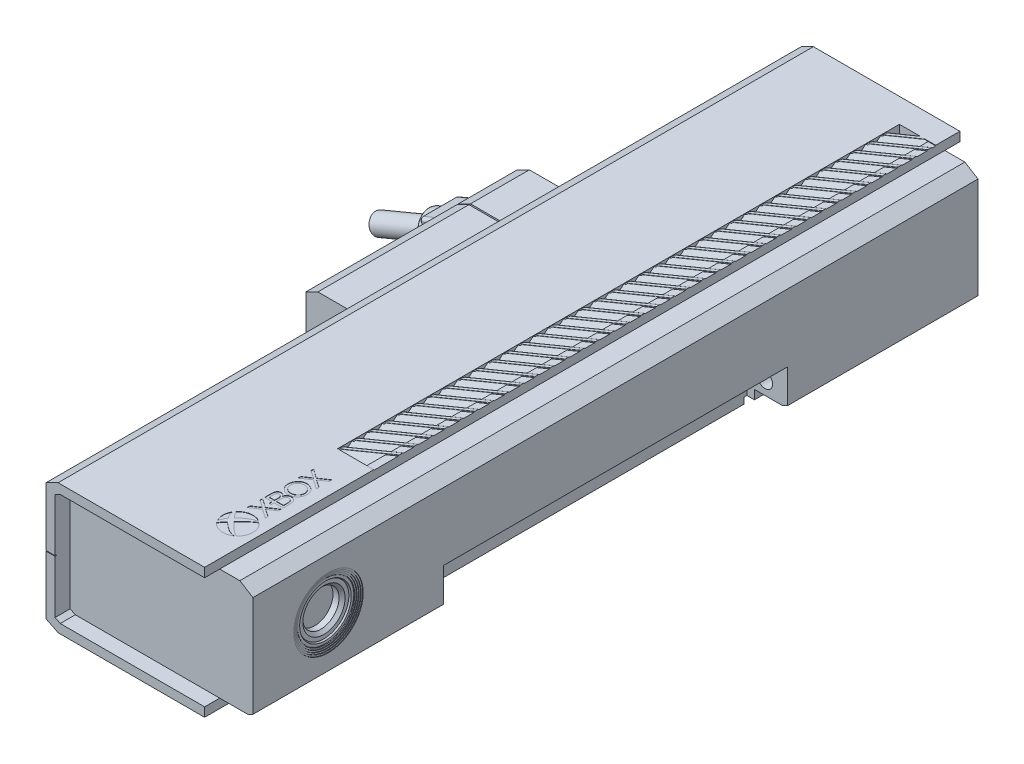
SolidWorks part; units mm, degrees
ref_plane "Front Plane" through (0, 0, 0) normal (0, 0, 1) x (1, 0, 0)
ref_plane "Top Plane" through (0, 0, 0) normal (0, 1, 0) x (1, 0, 0)
ref_plane "Right Plane" through (0, 0, 0) normal (1, 0, 0) x (0, 0, -1)
sketch "Sketch1" plane through (0, 0, 0) normal (0, 0, 1) x (1, 0, 0)
  line L1 (0, 0) -> (-66.5, 0)
  line L2 (0, 0) -> (0, 43)
  line L3 (0, 43) -> (-66.5, 43)
  line L4 (-66.5, 0) -> (-66.5, 43)
  dimension "D1" = 66.5
  dimension "D2" = 43
extrude "Boss-Extrude1" add sketch "Sketch1" along normal blind 250
sketch "Sketch2" plane through (0, 0, 0) normal (0, -1, 0) x (1, 0, 0)
  line L0 (-66.5, 250) -> (-66.5, 0) construction
  line L1 (-66.5, 181) -> (-16.5, 181)
  line L2 (-66.5, 181) -> (-66.5, 69)
  line L3 (-66.5, 69) -> (-16.5, 69)
  line L4 (-16.5, 181) -> (-16.5, 69)
  line L6 (-16.5, 125) -> (-66.5, 125) construction
  dimension "D1" = 112
  dimension "D2" = 50
extrude "Boss-Extrude2" add sketch "Sketch2" along normal blind 2
sketch "Sketch3" plane through (0, 0, 0) normal (0, -1, 0) x (1, 0, 0)
  line L0 (-16.5, 69) -> (-16.5, 181) construction
  line L1 (-16.5, 182) -> (-3, 182)
  line L2 (-16.5, 182) -> (-16.5, 68)
  line L3 (-16.5, 68) -> (-3, 68)
  line L4 (-3, 182) -> (-3, 68)
  line L5 (-3, 125) -> (-16.5, 125) construction
  line L6 (-16.5, 69) -> (-16.5, 181) construction
  line L7 (0, 250) -> (0, 0) construction
  dimension "D1" = 114
  dimension "D2" = 3
extrude "Cut-Extrude1" cut sketch "Sketch3" against normal blind 15
sketch "Sketch5" plane through (0, 0, 250) normal (0, 0, 1) x (1, 0, 0)
  line L0 (-6.5, 43) -> (0, 39)
  line L1 (0, 43) -> (-66.5, 43) construction
  line L2 (0, 0) -> (0, 43) construction
  line L3 (0, 39) -> (0, 43)
  line L4 (0, 43) -> (-6.5, 43)
  dimension "D1" = 6.5
  dimension "D2" = 4
extrude "Cut-Extrude2" cut sketch "Sketch5" against normal through all
sketch "Sketch6" plane through (0, 0, 250) normal (0, 0, 1) x (1, 0, 0)
  line L0 (-4, 0) -> (0, 2)
  line L1 (-66.5, 0) -> (0, 0) construction
  line L2 (0, 0) -> (0, 39) construction
  line L3 (0, 2) -> (0, 0)
  line L4 (0, 0) -> (-4, 0)
  dimension "D1" = 4
  dimension "D2" = 2
extrude "Cut-Extrude3" cut sketch "Sketch6" against normal through all
sketch "Sketch7" plane through (0, 0, 250) normal (0, 0, 1) x (1, 0, 0)
  line L5 (-6.5, 43) -> (-66.5, 43) construction
  line L6 (-6.5, 43) -> (0, 39) construction
  line L7 (0, 2) -> (0, 39) construction
  line L8 (0, 2) -> (-4, 0) construction
  line L9 (-66.5, 0) -> (-4, 0) construction
  line L10 (-66.5, 3) -> (-4.7082, 3)
  line L11 (-4.7082, 3) -> (-3, 3.8541)
  line L12 (-3, 3.8541) -> (-3, 37.3236)
  line L13 (-3, 37.3236) -> (-7.3491, 40)
  line L14 (-7.3491, 40) -> (-66.5, 40)
  line L15 (-14, 3) -> (-4.7082, 3)
  line L16 (-4.7082, 3) -> (-3, 3.8541)
  line L17 (-3, 3.8541) -> (-3, 37.3236)
  line L18 (-3, 37.3236) -> (-7.3491, 40)
  line L19 (-7.3491, 40) -> (-14, 40)
  line L20 (-6.5, 43) -> (-14, 43)
  line L21 (-6.5, 43) -> (0, 39)
  line L22 (0, 2) -> (0, 39)
  line L23 (0, 2) -> (-4, 0)
  line L24 (-14, 0) -> (-4, 0)
  line L25 (-14, 43) -> (-14, 40)
  line L26 (-14, 3) -> (-14, 0)
  dimension "D2" = 14
  dimension "D1" = 3
extrude "Cut-Extrude4" cut sketch "Sketch7" against normal through all
sketch "Sketch9" plane through (0, 0, 250) normal (0, 0, 1) x (1, 0, 0)
  line L0 (-62.5, 43) -> (-66.5, 41)
  line L1 (-14, 43) -> (-66.5, 43) construction
  line L2 (-66.5, 43) -> (-66.5, 0) construction
  line L3 (-66.5, 41) -> (-66.5, 43)
  line L4 (-66.5, 43) -> (-62.5, 43)
  line L5 (-66.5, 2) -> (-66.5, -2)
  line L6 (-66.5, -2) -> (-58.5, -2)
  line L7 (-16.5, -2) -> (-66.5, -2) construction
  line L8 (-58.5, -2) -> (-66.5, 2)
  line L9 (-66.5, 0) -> (-14, 0) construction
  line L11 (-16.5, 0) -> (-66.5, 0) construction
  point P16 (-62.5, 0)
  dimension "D1" = 4
  dimension "D2" = 2
  dimension "D3" = 2
  dimension "D4" = 4
extrude "Cut-Extrude5" cut sketch "Sketch9" against normal through all
sketch "Sketch10" plane through (-66.5, 0, 0) normal (-1, 0, 0) x (0, 0, 1)
  line L0 (0, 41) -> (250, 41) construction
  line L1 (100, 40.7) -> (150, 40.7)
  line L2 (100, 40.7) -> (100, -7.3)
  line L3 (100, -7.3) -> (150, -7.3)
  line L4 (150, 40.7) -> (150, -7.3)
  line L5 (125, 2) -> (125, -7.3) construction
  line L8 (0, 2) -> (250, 2) construction
  dimension "D1" = 0.3
  dimension "D2" = 48
  dimension "D3" = 50
extrude "Boss-Extrude3" add sketch "Sketch10" along normal blind 14
sketch "Sketch12" plane through (0, 0, 150) normal (0, 0, 1) x (1, 0, 0)
  line L0 (-80.5, -7.3) -> (-80.5, 40.7) construction
  line L1 (-80.5, -7.3) -> (-40.5, -7.3)
  line L2 (-80.5, -7.3) -> (-80.5, 2.7)
  line L3 (-80.5, 2.7) -> (-30.5, 2.7)
  line L4 (-30.5, -2) -> (-30.5, 2.7)
  line L5 (-30.5, -2) -> (-40.5, -7.3)
  line L6 (-58.5, -2) -> (-16.5, -2) construction
  dimension "D1" = 50
  dimension "D2" = 10
  dimension "D3" = 10
extrude "Boss-Extrude4" add sketch "Sketch12" against normal up to surface (50 mm away) up to face at (-72.1, 13.76, 100)
sketch "Sketch13" plane through (0, 0, 150) normal (0, 0, 1) x (1, 0, 0)
  line L0 (-80.5, 38.7) -> (-76.5, 40.7)
  line L1 (-80.5, -7.3) -> (-80.5, 40.7) construction
  line L2 (-80.5, 40.7) -> (-66.5, 40.7) construction
  line L3 (-76.5, 40.7) -> (-80.5, 40.7)
  line L4 (-80.5, 40.7) -> (-80.5, 38.7)
  dimension "D1" = 4
  dimension "D2" = 2
extrude "Cut-Extrude6" cut sketch "Sketch13" against normal through all
sketch "Sketch14" plane through (0, 0, 150) normal (0, 0, 1) x (1, 0, 0)
  line L0 (-80.5, -3.3) -> (-73.5, -7.3)
  line L1 (-80.5, -7.3) -> (-80.5, 38.7) construction
  line L2 (-80.5, -7.3) -> (-40.5, -7.3) construction
  line L3 (-73.5, -7.3) -> (-80.5, -7.3)
  line L4 (-80.5, -7.3) -> (-80.5, -3.3)
  dimension "D1" = 7
  dimension "D2" = 4
extrude "Cut-Extrude7" cut sketch "Sketch14" against normal through all
sketch "Sketch15" plane through (0, 0, 100) normal (0, 0, -1) x (-1, 0, 0)
  line L0 (76.5, 40.7) -> (66.5, 40.7) construction
  line L1 (80.5, 38.7) -> (76.5, 40.7) construction
  line L2 (80.5, 38.7) -> (80.5, -3.3) construction
  line L3 (76.5, 40.7) -> (66.5, 40.7)
  line L4 (80.5, 38.7) -> (76.5, 40.7)
  line L5 (80.5, 38.7) -> (80.5, 4)
  line L6 (66.5, 2) -> (76.5, 2)
  line L7 (76.5, 2) -> (80.5, 4)
  line L8 (66.5, 40.7) -> (66.5, 2)
  point P5 (80.5, 2)
  dimension "D1" = 4
  dimension "D2" = 2
extrude "Boss-Extrude5" add sketch "Sketch15" along normal offset from surface (20 mm away) 70 up to face at (-63.7222, 11.1333, 150)
sketch "Sketch16" plane through (0, 0, 100) normal (0, 0, -1) x (-1, 0, 0)
  line L6 (80.5, 4) -> (80.5, 38.7)
  line L7 (80.5, 38.7) -> (76.5, 40.7)
  line L8 (76.5, 40.7) -> (66.5, 40.7)
  line L9 (66.5, 40.7) -> (66.5, 2)
  line L10 (66.5, 2) -> (76.5, 2)
  line L11 (76.5, 2) -> (80.5, 4)
  line L12 (80.5, 4) -> (80.5, 38.7)
  line L13 (80.5, 38.7) -> (76.5, 40.7)
  line L14 (76.5, 40.7) -> (66.5, 40.7)
  line L15 (66.5, 41) -> (66.5, 2) construction
  line L16 (66.5, 2) -> (76.5, 2)
  line L17 (76.5, 2) -> (80.5, 4)
  line L18 (66.5, 40.7) -> (66.5, 40.2)
  line L19 (66.5, 40.7) -> (66.5, 2) construction
  line L20 (66.5, 2.5) -> (66.5, 2)
  line L24 (80, 4.309) -> (80, 38.391)
  line L25 (80, 38.391) -> (76.382, 40.2)
  line L26 (76.382, 40.2) -> (67, 40.2)
  line L27 (67, 40.2) -> (67, 2.5)
  line L28 (67, 2.5) -> (76.382, 2.5)
  line L29 (76.382, 2.5) -> (80, 4.309)
  line L30 (80, 4.309) -> (80, 38.391)
  line L31 (80, 38.391) -> (76.382, 40.2)
  line L32 (76.382, 40.2) -> (66.5, 40.2)
  line L34 (66.5, 2.5) -> (76.382, 2.5)
  line L35 (76.382, 2.5) -> (80, 4.309)
  dimension "D1" = 0
  dimension "D2" = 0.5
extrude "Cut-Extrude8" cut sketch "Sketch16" along normal blind 0.5
sketch "Sketch17" plane through (-80.5, 0, 0) normal (-1, 0, 0) x (0, 0, 1)
  line L0 (80, 40.7) -> (80, 2) construction
  line L1 (82, 35.7) -> (97.5, 35.7)
  line L2 (82, 35.7) -> (82, 7)
  line L3 (82, 7) -> (97.5, 7)
  line L4 (97.5, 35.7) -> (97.5, 7)
  line L5 (89.75, 38.7) -> (89.75, 35.7) construction
  line L6 (80, 38.7) -> (99.5, 38.7) construction
  line L7 (80, 40.7) -> (99.5, 40.7) construction
  line L8 (82, 21.35) -> (80, 21.35) construction
  line L9 (80, 4) -> (80, 38.7) construction
  dimension "D1" = 2
  dimension "D2" = 5
extrude "Cut-Extrude9" cut sketch "Sketch17" against normal blind 0.1
sketch "Sketch18" plane through (-80.4, 0, 0) normal (-1, 0, 0) x (0, 0, 1)
  line L0 (89.75, 31.7) -> (89.75, 35.7) construction
  line L1 (83.5, 31.7) -> (96, 31.7)
  line L2 (83.5, 31.7) -> (83.5, 18.7)
  line L3 (83.5, 18.7) -> (96, 18.7)
  line L4 (96, 31.7) -> (96, 18.7)
  line L5 (97.5, 35.7) -> (82, 35.7) construction
  line L6 (97.5, 35.7) -> (82, 35.7) construction
  dimension "D1" = 4
  dimension "D2" = 12.5
  dimension "D3" = 13
ref_plane "Plane1" through (0, 0, 89.75) normal (0, 0, 1) x (1, 0, 0)
sketch "Sketch19" plane through (0, 0, 89.75) normal (0, 0, 1) x (1, 0, 0)
  line L0 (-80.4, 31.7) -> (-96.5, 24.9917)
  line L1 (-80.4, 31.7) -> (-80.4, 18.7)
  line L2 (-80.4, 18.7) -> (-91.8846, 13.9147)
  line L3 (-96.5, 24.9917) -> (-91.8846, 13.9147)
  line L4 (-80.5, -3.3) -> (-80.5, 38.7) construction
  dimension "D1" = 16
  dimension "D2" = 12
extrude "Boss-Extrude6" add sketch "Sketch19" along normal mid plane 13
sketch "Sketch20" plane through (-73.3521, -30.5634, 0) normal (-0.9231, -0.3846, 0) x (0, 0, 1)
  line L0 (89.75, 60.1846) -> (89.75, 48.1846) construction
  line L1 (96.25, 60.1846) -> (83.25, 60.1846) construction
  line L2 (96.25, 48.1846) -> (83.25, 48.1846) construction
  circle A0 centre (89.75, 54.1846) radius 5.5
  dimension "D1" = 11
extrude "Boss-Extrude7" add sketch "Sketch20" along normal blind 4
sketch "Sketch21" plane through (-77.0444, -32.1018, 0) normal (-0.9231, -0.3846, 0) x (0, 0, 1)
  circle A0 centre (89.75, 54.1846) radius 3.25
  dimension "D1" = 6.5
extrude "Boss-Extrude8" add sketch "Sketch21" along normal blind 20
sketch "Sketch22" plane through (0, 0, 182) normal (0, 0, -1) x (-1, 0, 0)
  line L0 (3, 37.3236) -> (3, 3.8541) construction
  line L1 (4.7082, 3) -> (14, 3) construction
  circle A0 centre (10.5, 7.5) radius 2.5
  dimension "D1" = 5
  dimension "D2" = 7.5
  dimension "D3" = 4.5
extrude "Cut-Extrude10" cut sketch "Sketch22" against normal blind 10
ref_plane "Plane2" through (0, 0, 125) normal (0, 0, -1) x (-1, 0, 0)
mirror "Mirror1" about plane through (0, 0, 125) normal (0, 0, -1) of "Cut-Extrude10"
sketch "Sketch23" plane through (0, 0, 250) normal (0, 0, 1) x (1, 0, 0)
  line L10 (-61.7918, 3) -> (-14, 3)
  line L11 (-63.5, 3.8541) -> (-61.7918, 3)
  line L12 (-63.5, 39.1459) -> (-63.5, 3.8541)
  line L13 (-61.7918, 40) -> (-63.5, 39.1459)
  line L14 (-14, 40) -> (-61.7918, 40)
  line L15 (-61.7918, 3) -> (-14, 3)
  line L16 (-63.5, 3.8541) -> (-61.7918, 3)
  line L17 (-63.5, 39.1459) -> (-63.5, 3.8541)
  line L18 (-61.7918, 40) -> (-63.5, 39.1459)
  line L19 (-14, 40) -> (-61.7918, 40)
  line L20 (-14, 40) -> (-7.3491, 40) construction
  line L21 (-7.3491, 40) -> (-3, 37.3236) construction
  line L22 (-3, 37.3236) -> (-3, 3.8541) construction
  line L23 (-3, 3.8541) -> (-4.7082, 3) construction
  line L24 (-4.7082, 3) -> (-14, 3) construction
  line L25 (-14, 40) -> (-7.3491, 40)
  line L26 (-7.3491, 40) -> (-3, 37.3236)
  line L27 (-3, 37.3236) -> (-3, 3.8541)
  line L28 (-3, 3.8541) -> (-4.7082, 3)
  line L29 (-4.7082, 3) -> (-14, 3)
  dimension "D1" = 3
extrude "Cut-Extrude11" cut sketch "Sketch23" against normal blind 5
mirror "Mirror2" about plane through (0, 0, 125) normal (0, 0, -1) of "Cut-Extrude11"
fillet "Fillet1" radius 1 4 edges at (-86.1423, 16.3074, 83.25) (-86.1423, 16.3074, 96.25) (-88.45, 28.3458, 83.25) (-88.45, 28.3458, 96.25)
fillet "Fillet2" radius 0.2 11 edges at (-96.6346, 14.9147, 89.75) (-95.7692, 12.8378, 89.75) (-96.3077, 24.5301, 89.75) (-96.3873, 24.7213, 83.5429) (-96.5, 24.9917, 89.75) (-96.3873, 24.7213, 95.9571) (-94.1923, 19.4532, 96.25) (-91.9973, 14.1851, 95.9571) (-91.8846, 13.9147, 89.75) (-91.9973, 14.1851, 83.5429) (-94.1923, 19.4532, 83.25)
fillet "Fillet3" radius 0.2 4 edges at (-80.45, 35.7, 97.5) (-80.45, 7, 97.5) (-80.45, 7, 82) (-80.45, 35.7, 82)
ref_plane "Plane3" through (0, 21.5, 0) normal (0, -1, 0) x (-1, 0, 0)
sketch "Sketch25" plane through (0, 21.5, 0) normal (0, -1, 0) x (-1, 0, 0)
  line L0 (66.5, 0) -> (66.5, -80)
  line L1 (66.5, -80) -> (66, -80)
  line L2 (63.5, 0) -> (63.5, -0.5)
  line L3 (63.5, -0.5) -> (66, -0.5)
  line L4 (66, -0.5) -> (66, -80)
  line L5 (62.5, 0) -> (14, 0) construction
  line L6 (63.5, 0) -> (66.5, 0)
  line L7 (80.5, -125) -> (167.176, -125) construction
  line L8 (80.5, -150) -> (80.5, -100) construction
  line L9 (63.5, -250) -> (66.5, -250)
  line L10 (63.5, -250) -> (63.5, -249.5)
  line L11 (63.5, -249.5) -> (66, -249.5)
  line L12 (66.5, -250) -> (66.5, -150)
  line L14 (66, -249.5) -> (66, -150)
  line L15 (73.5, -150) -> (40.5, -150) construction
  line L16 (66, -150) -> (66.5, -150)
  dimension "D1" = 0.5
  dimension "D2" = 0.5
extrude "Cut-Extrude12" cut sketch "Sketch25" against normal mid plane 0.2
sketch "Sketch26" plane through (-80.5, 0, 0) normal (-1, 0, 0) x (0, 0, 1)
  line L8 (147, 35.7) -> (103, 35.7)
  line L9 (103, 35.7) -> (103, -0.3)
  line L10 (103, -0.3) -> (147, -0.3)
  line L11 (147, -0.3) -> (147, 35.7)
  line L12 (147, 35.7) -> (103, 35.7)
  line L13 (103, 35.7) -> (103, -0.3)
  line L14 (103, -0.3) -> (147, -0.3)
  line L15 (147, -0.3) -> (147, 35.7)
  dimension "D1" = 3
extrude "Cut-Extrude13" cut sketch "Sketch26" against normal blind 8
sketch "Sketch28" plane through (0, 43, 0) normal (0, 1, 0) x (1, 0, 0)
  line L1 (-26, -8) -> (-14, -8)
  line L2 (-26, -8) -> (-26, -194)
  line L3 (-26, -194) -> (-14, -194)
  line L4 (-14, -8) -> (-14, -194)
  line L5 (-14, 0) -> (-14, -250) construction
  line L9 (-14, 0) -> (-62.5, 0) construction
  dimension "D1" = 186
  dimension "D2" = 12
  dimension "D3" = 8
extrude "Cut-Extrude14" cut sketch "Sketch28" against normal blind 0.2
sketch "Sketch29" plane through (0, 42.8, 0) normal (0, 1, 0) x (1, 0, 0)
  line L1 (-26, -8) -> (-16.5, -8)
  line L2 (-26, -8) -> (-26, -194)
  line L3 (-26, -194) -> (-16.5, -194)
  line L4 (-16.5, -8) -> (-16.5, -194)
  line L5 (-26, -194) -> (-14, -194) construction
  dimension "D1" = 9.5
extrude "Cut-Extrude15" cut sketch "Sketch29" against normal blind 5
ref_plane "Plane4" through (-21.205, 0, 14.8479) normal (0.8192, 0, -0.5736) x (0, 1, 0)
sketch "Sketch32" plane through (-21.205, 0, 14.8479) normal (0.8192, 0, -0.5736) x (0, 1, 0)
  line L0 (43, -3.4456) -> (37.8, 1.7544)
  line L1 (43, -8.3598) -> (43, 144.0025) construction
  line L2 (37.8, -8.3598) -> (37.8, 144.0025) construction
  line L3 (37.8, 1.7544) -> (37.8, 0.3402)
  line L4 (37.8, 0.3402) -> (43, -4.8598)
  line L5 (43, -4.8598) -> (43, -3.4456)
  dimension "D1" = 1
  dimension "D2" = 45
  dimension "D3" = 3.5
extrude "Boss-Extrude9" add sketch "Sketch32" against normal blind 8 and the other way up to surface other way up to face at (-14, 41.76, 115.4)
fillet "Fillet4" radius 0.2 2 edges at (-22.949, 43, 10.1364) (-21.7162, 43, 10.9996)
pattern_linear "LPattern1" count 37 spacing 5 along (0, 0, 1) of "Boss-Extrude9", "Fillet4"
sketch "Sketch34" plane through (0, 43, 0) normal (0, 1, 0) x (1, 0, 0)
  line L0 (-26, -194) -> (-14, -194) construction
  line L1 (-26, -8) -> (-25.5, -8)
  line L2 (-26, -8) -> (-26, -194)
  line L3 (-26, -194) -> (-25.5, -194)
  line L4 (-25.5, -8) -> (-25.5, -194)
  dimension "D1" = 0.5
extrude "Cut-Extrude17" cut sketch "Sketch34" against normal up to surface (0.2 mm away) up to face at (-15.25, 42.8, 190.358)
sketch "Sketch35" plane through (-3, 0, 0) normal (1, 0, 0) x (0, 0, -1)
  line L0 (-250, 39.1459) -> (-250, 21.6) construction
  line L1 (-194, 43) -> (-250, 43) construction
  circle A0 centre (-220, 20.5148) radius 11.5
  dimension "D1" = 23
  dimension "D2" = 30
  dimension "D3" = 22.4852
extrude "Cut-Extrude19" cut sketch "Sketch35" against normal blind 0.2
sketch "Sketch36" plane through (-3.2, 0, 0) normal (1, 0, 0) x (0, 0, -1)
  circle A2 centre (-220, 20.5148) radius 11
  circle A3 centre (-220, 20.5148) radius 11
  dimension "D1" = 0.5
extrude "Cut-Extrude20" cut sketch "Sketch36" against normal blind 0.2
sketch "Sketch37" plane through (-3.4, 0, 0) normal (1, 0, 0) x (0, 0, -1)
  circle A2 centre (-220, 20.5148) radius 10.5
  circle A3 centre (-220, 20.5148) radius 10.5
  dimension "D1" = 0.5
extrude "Cut-Extrude21" cut sketch "Sketch37" against normal blind 0.2
sketch "Sketch38" plane through (-3.6, 0, 0) normal (1, 0, 0) x (0, 0, -1)
  circle A2 centre (-220, 20.5148) radius 10
  circle A3 centre (-220, 20.5148) radius 10
  dimension "D1" = 0.5
extrude "Cut-Extrude22" cut sketch "Sketch38" against normal blind 0.2
sketch "Sketch40" plane through (-3.8, 0, 0) normal (1, 0, 0) x (0, 0, -1)
  circle A2 centre (-220, 20.5148) radius 9.5
  circle A3 centre (-220, 20.5148) radius 9.5
  dimension "D1" = 0.5
extrude "Cut-Extrude24" cut sketch "Sketch40" against normal blind 0.2
sketch "Sketch39" plane through (-4, 0, 0) normal (1, 0, 0) x (0, 0, -1)
  circle A3 centre (-220, 20.5148) radius 8.75
  circle A4 centre (-220, 20.5148) radius 8.75
  dimension "D1" = 0.75
extrude "Cut-Extrude23" cut sketch "Sketch39" against normal blind 0.5
chamfer "Chamfer1" distance 0.5 angle 60 1 edges at (-4.5, 29.2648, 220) first distance on face at (-4.5, 29.2648, 220)
sketch "Sketch41" plane through (-4, 0, 0) normal (1, 0, 0) x (0, 0, -1)
  circle A1 centre (-220, 20.5148) radius 9.5
  circle A2 centre (-220, 20.5148) radius 9.5
  circle A4 centre (-220, 20.5148) radius 9.3
  circle A5 centre (-220, 20.5148) radius 9.3
  dimension "D1" = 0
  dimension "D2" = 0.2
extrude "Cut-Extrude25" cut sketch "Sketch41" against normal blind 0.1
sketch "Sketch42" plane through (-4.5, 0, 0) normal (1, 0, 0) x (0, 0, -1)
  circle A0 centre (-220, 20.5148) radius 7
  dimension "D1" = 14
extrude "Cut-Extrude26" cut sketch "Sketch42" against normal blind 1 contours A0
chamfer "Chamfer2" distance 1 angle 45 1 edges at (-5.5, 27.5148, 220)
sketch "Sketch43" plane through (-5.5, 0, 0) normal (1, 0, 0) x (0, 0, -1)
  circle A1 centre (-220, 20.5148) radius 6
  circle A2 centre (-220, 20.5148) radius 6
  dimension "D1" = 0
extrude "Cut-Extrude27" cut sketch "Sketch43" against normal blind 2
sketch "Sketch44" plane through (0, 43, 0) normal (0, 1, 0) x (1, 0, 0)
  line L0 (-14, -250) -> (-62.5, -250) construction
  line L1 (-14, -194) -> (-14, -250) construction
  circle B0 centre (-20.9812, -232.0188) radius 4.9812
  spline B1 degree 2 poles (-24.79, -235.2289) (-24.1424, -234.0184) (-23.21, -233.2202) knots 0 0 0 1 1 1
  spline B2 degree 2 poles (-25.2689, -234.554) (-25.1923, -233.5043) (-24.1914, -232.0188) knots 0 0 0 1 1 1
  spline B3 degree 2 poles (-24.1914, -232.0188) (-25.1226, -230.7707) (-25.2689, -229.4837) knots 0 0 0 1 1 1
  spline B4 degree 2 poles (-23.21, -230.8319) (-24.4289, -229.7002) (-24.7527, -228.765) knots 0 0 0 1 1 1
  spline B5 degree 2 poles (-23.21, -230.8319) (-20.2779, -228.0841) (-18.1373, -227.9293) knots 0 0 0 1 1 1
  spline B6 degree 2 poles (-23.21, -233.2202) (-20.4006, -235.9032) (-18.1208, -236.0968) knots 0 0 0 1 1 1
  spline B7 degree 2 poles (-17.75, -235.8098) (-19.8183, -234.7439) (-22.2056, -232.0188) knots 0 0 0 1 1 1
  spline B8 degree 2 poles (-22.2056, -232.0188) (-18.8809, -228.4451) (-17.727, -228.2476) knots 0 0 0 1 1 1
  spline B9 degree 3 poles (-20.9667, -220.001) (-19.976, -220.001) (-18.992, -220.0011) (-18, -220.0012) knots 26 26 26 26 27 27 27 27
  spline B10 degree 3 poles (-20.9668, -221.2297) (-20.9668, -220.8151) (-20.9668, -220.41) (-20.9667, -220.001) knots 25 25 25 25 26 26 26 26
  spline B11 degree 3 poles (-21.1127, -221.1437) (-21.0673, -221.1709) (-21.0215, -221.1975) (-20.9668, -221.2297) knots 24 24 24 24 25 25 25 25
  spline B12 degree 3 poles (-21.6158, -220.8437) (-21.4474, -220.9424) (-21.2803, -221.0436) (-21.1127, -221.1437) knots 23 23 23 23 24 24 24 24
  spline B13 degree 3 poles (-21.6529, -220.7758) (-21.653, -220.8074) (-21.6448, -220.8267) (-21.6158, -220.8437) knots 22 22 22 22 23 23 23 23
  spline B14 degree 3 poles (-21.6523, -220.0716) (-21.652, -220.3063) (-21.6517, -220.5411) (-21.6529, -220.7758) knots 21 21 21 21 22 22 22 22
  spline B15 degree 3 poles (-21.7217, -220) (-21.644, -220) (-21.6524, -219.9903) (-21.6523, -220.0716) knots 20 20 20 20 21 21 21 21
  spline B16 degree 3 poles (-24.107, -219.9997) (-24.0829, -219.9997) (-24.0626, -219.9997) (-24.0423, -219.9997) (-23.2688, -219.9998) (-22.4953, -219.9997) (-21.7217, -220) knots 18 18 18 18 19 19 19 20 20 20 20
  spline B17 degree 3 poles (-24.1101, -219.9561) (-24.1101, -219.9697) (-24.1082, -219.9833) (-24.107, -219.9997) knots 17 17 17 17 18 18 18 18
  spline B18 degree 3 poles (-24.1058, -217.905) (-24.1138, -218.5886) (-24.1096, -219.2724) (-24.1101, -219.9561) knots 16 16 16 16 17 17 17 17
  spline B19 degree 3 poles (-24.0487, -217.1332) (-24.0844, -217.3882) (-24.1027, -217.6474) (-24.1058, -217.905) knots 15 15 15 15 16 16 16 16
  spline B20 degree 3 poles (-23.7151, -216.3354) (-23.8974, -216.5714) (-24.0078, -216.8415) (-24.0487, -217.1332) knots 14 14 14 14 15 15 15 15
  spline B21 degree 3 poles (-23.0053, -215.9346) (-23.2921, -215.978) (-23.5351, -216.1022) (-23.7151, -216.3354) knots 13 13 13 13 14 14 14 14
  spline B22 degree 3 poles (-22.1991, -216.0209) (-22.4577, -215.9052) (-22.7295, -215.8928) (-23.0053, -215.9346) knots 12 12 12 12 13 13 13 13
  spline B23 degree 3 poles (-21.5789, -216.5974) (-21.7324, -216.3481) (-21.9279, -216.1424) (-22.1991, -216.0209) knots 11 11 11 11 12 12 12 12
  spline B24 degree 3 poles (-21.5202, -216.6998) (-21.541, -216.6665) (-21.5583, -216.6309) (-21.5789, -216.5974) knots 10 10 10 10 11 11 11 11
  spline B25 degree 3 poles (-21.4904, -216.7251) (-21.5005, -216.7168) (-21.5136, -216.7104) (-21.5202, -216.6998) knots 9 9 9 9 10 10 10 10
  spline B26 degree 3 poles (-21.4696, -216.6932) (-21.4724, -216.7048) (-21.4833, -216.7145) (-21.4904, -216.7251) knots 8 8 8 8 9 9 9 9
  spline B27 degree 3 poles (-21.2891, -216.1977) (-21.375, -216.3533) (-21.4283, -216.5211) (-21.4696, -216.6932) knots 7 7 7 7 8 8 8 8
  spline B28 degree 3 poles (-20.0698, -215.403) (-20.6163, -215.4523) (-21.0236, -215.7169) (-21.2891, -216.1977) knots 6 6 6 6 7 7 7 7
  spline B29 degree 3 poles (-19.2495, -215.4926) (-19.5156, -215.399) (-19.7907, -215.3778) (-20.0698, -215.403) knots 5 5 5 5 6 6 6 6
  spline B30 degree 3 poles (-18.3984, -216.1666) (-18.6103, -215.8499) (-18.8889, -215.6194) (-19.2495, -215.4926) knots 4 4 4 4 5 5 5 5
  spline B31 degree 3 poles (-18.0329, -217.2174) (-18.0697, -216.8389) (-18.1849, -216.4856) (-18.3984, -216.1666) knots 3 3 3 3 4 4 4 4
  spline B32 degree 3 poles (-18.0014, -217.8588) (-18.0025, -217.6449) (-18.0122, -217.4303) (-18.0329, -217.2174) knots 2 2 2 2 3 3 3 3
  spline B33 degree 3 poles (-18, -220.0012) (-18, -219.9754) (-18, -219.9569) (-18, -219.9383) (-18, -219.2451) (-17.9976, -218.5519) (-18.0014, -217.8588) knots 0 0 0 0 1 1 1 2 2 2 2
  spline B34 degree 3 poles (-23.0888, -214.5405) (-22.5311, -215.0721) (-21.8691, -215.3472) (-21.0953, -215.3438) knots 13 13 13 13 14 14 14 14
  spline B35 degree 3 poles (-23.8778, -213.4318) (-23.6936, -213.8575) (-23.4231, -214.2221) (-23.0888, -214.5405) knots 12 12 12 12 13 13 13 13
  spline B36 degree 3 poles (-24.1062, -212.1126) (-24.1283, -212.5693) (-24.0603, -213.0103) (-23.8778, -213.4318) knots 11 11 11 11 12 12 12 12
  spline B37 degree 3 poles (-23.8435, -210.939) (-24.0073, -211.3122) (-24.0865, -211.7062) (-24.1062, -212.1126) knots 10 10 10 10 11 11 11 11
  spline B38 degree 3 poles (-22.6742, -209.5009) (-23.2164, -209.8557) (-23.5863, -210.3529) (-23.8435, -210.939) knots 9 9 9 9 10 10 10 10
  spline B39 degree 3 poles (-21.4631, -209.0796) (-21.8983, -209.129) (-22.3061, -209.2602) (-22.6742, -209.5009) knots 8 8 8 8 9 9 9 9
  spline B40 degree 3 poles (-20.4379, -209.1132) (-20.7777, -209.044) (-21.12, -209.0406) (-21.4631, -209.0796) knots 7 7 7 7 8 8 8 8
  spline B41 degree 3 poles (-19.0528, -209.7929) (-19.461, -209.4578) (-19.9171, -209.2191) (-20.4379, -209.1132) knots 6 6 6 6 7 7 7 7
  spline B42 degree 3 poles (-18.2028, -210.8307) (-18.4097, -210.4223) (-18.7003, -210.0821) (-19.0528, -209.7929) knots 5 5 5 5 6 6 6 6
  spline B43 degree 3 poles (-17.9177, -211.8091) (-17.9521, -211.4656) (-18.0467, -211.139) (-18.2028, -210.8307) knots 4 4 4 4 5 5 5 5
  spline B44 degree 3 poles (-18.0273, -213.0912) (-17.9075, -212.6715) (-17.8743, -212.2431) (-17.9177, -211.8091) knots 3 3 3 3 4 4 4 4
  spline B45 degree 3 poles (-20.4844, -215.2904) (-19.2513, -215.0993) (-18.3355, -214.1714) (-18.0273, -213.0912) knots 2 2 2 2 3 3 3 3
  spline B46 degree 3 poles (-21.094, -215.3564) (-20.8907, -215.3349) (-20.6862, -215.3217) (-20.4844, -215.2904) knots 1 1 1 1 2 2 2 2
  spline B47 degree 3 poles (-21.0953, -215.3438) (-21.0949, -215.348) (-21.0944, -215.3522) (-21.094, -215.3564) knots 0 0 0 0 1 1 1 1
  spline B48 degree 3 poles (-23.76, -204.0569) (-23.8733, -203.9778) (-23.9868, -203.8989) (-24.1065, -203.8154) knots 33 33 33 33 34 34 34 34
  spline B49 degree 3 poles (-21.842, -205.3956) (-22.4813, -204.9492) (-23.1207, -204.503) (-23.76, -204.0569) knots 32 32 32 32 33 33 33 33
  spline B50 degree 3 poles (-21.1377, -205.889) (-21.3714, -205.7231) (-21.6069, -205.5597) (-21.842, -205.3956) knots 31 31 31 31 32 32 32 32
  spline B51 degree 3 poles (-21.0399, -205.89) (-21.0774, -205.9156) (-21.1013, -205.9149) (-21.1377, -205.889) knots 30 30 30 30 31 31 31 31
  spline B52 degree 3 poles (-18.0252, -203.8361) (-19.0304, -204.5203) (-20.0356, -205.2045) (-21.0399, -205.89) knots 29 29 29 29 30 30 30 30
  spline B53 degree 3 poles (-18.0041, -203.8238) (-18.0145, -203.8299) (-18.0201, -203.8326) (-18.0252, -203.8361) knots 28 28 28 28 29 29 29 29
  spline B54 degree 3 poles (-17.9993, -203.8603) (-17.9993, -203.8492) (-18.0023, -203.8379) (-18.0041, -203.8238) knots 27 27 27 27 28 28 28 28
  spline B55 degree 3 poles (-18.0004, -204.7207) (-17.9986, -204.4338) (-17.9991, -204.1472) (-17.9993, -203.8603) knots 26 26 26 26 27 27 27 27
  spline B56 degree 3 poles (-18.0296, -204.777) (-18.0138, -204.7666) (-18.0006, -204.7399) (-18.0004, -204.7207) knots 25 25 25 25 26 26 26 26
  spline B57 degree 3 poles (-19.869, -205.9958) (-19.2556, -205.5899) (-18.6421, -205.1841) (-18.0296, -204.777) knots 24 24 24 24 25 25 25 25
  spline B58 degree 3 poles (-20.472, -206.3948) (-20.271, -206.2617) (-20.07, -206.1288) (-19.869, -205.9958) knots 23 23 23 23 24 24 24 24
  spline B59 degree 3 poles (-20.51, -206.4234) (-20.494, -206.4114) (-20.4835, -206.4024) (-20.472, -206.3948) knots 22 22 22 22 23 23 23 23
  spline B60 degree 3 poles (-20.4039, -206.4975) (-20.4384, -206.4739) (-20.4725, -206.4497) (-20.51, -206.4234) knots 21 21 21 21 22 22 22 22
  spline B61 degree 3 poles (-18.0304, -208.1079) (-18.8212, -207.5705) (-19.6126, -207.034) (-20.4039, -206.4975) knots 20 20 20 20 21 21 21 21
  spline B62 degree 3 poles (-18.0003, -208.1546) (-18.0003, -208.1387) (-18.016, -208.1177) (-18.0304, -208.1079) knots 19 19 19 19 20 20 20 20
  spline B63 degree 3 poles (-17.9995, -208.9911) (-17.9992, -208.7124) (-17.9986, -208.4335) (-18.0003, -208.1546) knots 18 18 18 18 19 19 19 19
  spline B64 degree 3 poles (-18.0049, -209.0081) (-18.0021, -208.9997) (-17.9995, -208.9955) (-17.9995, -208.9911) knots 17 17 17 17 18 18 18 18
  spline B65 degree 3 poles (-18.045, -208.9834) (-18.0327, -208.992) (-18.0193, -208.9993) (-18.0049, -209.0081) knots 16 16 16 16 17 17 17 17
  spline B66 degree 3 poles (-21.0015, -206.9199) (-20.0167, -207.6086) (-19.0308, -208.296) (-18.045, -208.9834) knots 15 15 15 15 16 16 16 16
  spline B67 degree 3 poles (-21.1039, -206.9202) (-21.0655, -206.894) (-21.0407, -206.8924) (-21.0015, -206.9199) knots 14 14 14 14 15 15 15 15
  spline B68 degree 3 poles (-23.2991, -208.4146) (-22.5672, -207.9167) (-21.835, -207.4193) (-21.1039, -206.9202) knots 13 13 13 13 14 14 14 14
  spline B69 degree 3 poles (-24.0609, -208.9328) (-23.807, -208.7601) (-23.5531, -208.5873) (-23.2991, -208.4146) knots 12 12 12 12 13 13 13 13
  spline B70 degree 3 poles (-24.1057, -208.9615) (-24.0871, -208.9496) (-24.0738, -208.9416) (-24.0609, -208.9328) knots 11 11 11 11 12 12 12 12
  spline B71 degree 3 poles (-24.1094, -208.9183) (-24.1094, -208.9313) (-24.1073, -208.9442) (-24.1057, -208.9615) knots 10 10 10 10 11 11 11 11
  spline B72 degree 3 poles (-24.1101, -208.0724) (-24.1091, -208.3543) (-24.1096, -208.6363) (-24.1094, -208.9183) knots 9 9 9 9 10 10 10 10
  spline B73 degree 3 poles (-24.076, -208.0071) (-24.1018, -208.0242) (-24.1102, -208.0423) (-24.1101, -208.0724) knots 8 8 8 8 9 9 9 9
  spline B74 degree 3 poles (-22.1532, -206.7344) (-22.794, -207.1589) (-23.4347, -207.5835) (-24.076, -208.0071) knots 7 7 7 7 8 8 8 8
  spline B75 degree 3 poles (-21.6726, -206.416) (-21.8328, -206.5223) (-21.993, -206.6283) (-22.1532, -206.7344) knots 6 6 6 6 7 7 7 7
  spline B76 degree 3 poles (-21.6297, -206.3846) (-21.6477, -206.3978) (-21.6598, -206.4075) (-21.6726, -206.416) knots 5 5 5 5 6 6 6 6
  spline B77 degree 3 poles (-21.8544, -206.2315) (-21.7807, -206.2814) (-21.7072, -206.3317) (-21.6297, -206.3846) knots 4 4 4 4 5 5 5 5
  spline B78 degree 3 poles (-24.0726, -204.729) (-23.3331, -205.2297) (-22.5938, -205.7305) (-21.8544, -206.2315) knots 3 3 3 3 4 4 4 4
  spline B79 degree 3 poles (-24.1102, -204.6704) (-24.1103, -204.7016) (-24.0941, -204.7145) (-24.0726, -204.729) knots 2 2 2 2 3 3 3 3
  spline B80 degree 3 poles (-24.1091, -203.8433) (-24.1093, -204.1189) (-24.1087, -204.3946) (-24.1102, -204.6704) knots 1 1 1 1 2 2 2 2
  spline B81 degree 3 poles (-24.1065, -203.8154) (-24.108, -203.8309) (-24.1091, -203.8371) (-24.1091, -203.8433) knots 0 0 0 0 1 1 1 1
  spline B82 degree 3 poles (-24.1113, -224.9343) (-24.11, -225.2132) (-24.1105, -225.4921) (-24.1106, -225.7709) (-24.1106, -225.786) (-24.1106, -225.8012) (-24.1106, -225.8233) knots 34 34 34 34 35 35 35 36 36 36 36
  spline B83 degree 3 poles (-24.0747, -224.8661) (-24.1016, -224.8838) (-24.1114, -224.9024) (-24.1113, -224.9343) knots 33 33 33 33 34 34 34 34
  spline B84 degree 3 poles (-21.6673, -223.2725) (-22.4696, -223.804) (-23.2718, -224.3354) (-24.0747, -224.8661) knots 32 32 32 32 33 33 33 33
  spline B85 degree 3 poles (-21.6303, -223.2454) (-21.645, -223.2562) (-21.6557, -223.2649) (-21.6673, -223.2725) knots 31 31 31 31 32 32 32 32
  spline B86 degree 3 poles (-22.0012, -222.9935) (-21.8788, -223.0765) (-21.7565, -223.1597) (-21.6303, -223.2454) knots 30 30 30 30 31 31 31 31
  spline B87 degree 3 poles (-24.0676, -221.5955) (-23.3783, -222.0607) (-22.6898, -222.5272) (-22.0012, -222.9935) knots 29 29 29 29 30 30 30 30
  spline B88 degree 3 poles (-24.1112, -221.5112) (-24.1115, -221.5501) (-24.1005, -221.5733) (-24.0676, -221.5955) knots 28 28 28 28 29 29 29 29
  spline B89 degree 3 poles (-24.1103, -220.678) (-24.1103, -220.7021) (-24.1103, -220.7191) (-24.1103, -220.7361) (-24.1103, -220.9945) (-24.1094, -221.2529) (-24.1112, -221.5112) knots 26 26 26 26 27 27 27 28 28 28 28
  spline B90 degree 3 poles (-24.066, -220.7052) (-24.0782, -220.6967) (-24.0915, -220.6895) (-24.1103, -220.678) knots 25 25 25 25 26 26 26 26
  spline B91 degree 3 poles (-22.2797, -221.9519) (-22.8751, -221.5363) (-23.4705, -221.1208) (-24.066, -220.7052) knots 24 24 24 24 25 25 25 25
  spline B92 degree 3 poles (-21.1253, -222.7584) (-21.5096, -222.4889) (-21.8947, -222.2206) (-22.2797, -221.9519) knots 23 23 23 23 24 24 24 24
  spline B93 degree 3 poles (-21.0554, -222.76) (-21.0827, -222.7786) (-21.0997, -222.7764) (-21.1253, -222.7584) knots 22 22 22 22 23 23 23 23
  spline B94 degree 3 poles (-18.8683, -221.2703) (-19.5975, -221.7667) (-20.3268, -222.2627) (-21.0554, -222.76) knots 21 21 21 21 22 22 22 22
  spline B95 degree 3 poles (-18.056, -220.7171) (-18.3269, -220.9014) (-18.5976, -221.086) (-18.8683, -221.2703) knots 20 20 20 20 21 21 21 21
  spline B96 degree 3 poles (-18.0029, -220.6836) (-18.0249, -220.6974) (-18.0408, -220.7067) (-18.056, -220.7171) knots 19 19 19 19 20 20 20 20
  spline B97 degree 3 poles (-18.0002, -220.7393) (-18.0002, -220.7228) (-18.0018, -220.7064) (-18.0029, -220.6836) knots 18 18 18 18 19 19 19 19
  spline B98 degree 3 poles (-17.9992, -221.5711) (-18.0008, -221.2938) (-18.0001, -221.0166) (-18.0002, -220.7393) knots 17 17 17 17 18 18 18 18
  spline B99 degree 3 poles (-18.0407, -221.6468) (-18.011, -221.6273) (-17.999, -221.6074) (-17.9992, -221.5711) knots 16 16 16 16 17 17 17 17
  spline B100 degree 3 poles (-19.9442, -222.9058) (-19.3099, -222.4859) (-18.6757, -222.0659) (-18.0407, -221.6468) knots 15 15 15 15 16 16 16 16
  spline B101 degree 3 poles (-20.4838, -223.2635) (-20.304, -223.1442) (-20.1241, -223.0249) (-19.9442, -222.9058) knots 14 14 14 14 15 15 15 15
  spline B102 degree 3 poles (-20.5107, -223.2835) (-20.4986, -223.2746) (-20.4915, -223.2686) (-20.4838, -223.2635) knots 13 13 13 13 14 14 14 14
  spline B103 degree 3 poles (-20.4678, -223.3152) (-20.4816, -223.3059) (-20.4946, -223.2955) (-20.5107, -223.2835) knots 12 12 12 12 13 13 13 13
  spline B104 degree 3 poles (-18.7395, -224.4876) (-19.3157, -224.0968) (-19.8917, -223.7061) (-20.4678, -223.3152) knots 11 11 11 11 12 12 12 12
  spline B105 degree 3 poles (-18.0361, -224.9657) (-18.2698, -224.8053) (-18.5048, -224.6467) (-18.7395, -224.4876) knots 10 10 10 10 11 11 11 11
  spline B106 degree 3 poles (-18.0019, -225.0199) (-18.002, -225.0015) (-18.0195, -224.9771) (-18.0361, -224.9657) knots 9 9 9 9 10 10 10 10
  spline B107 degree 3 poles (-18.0006, -225.8423) (-18.0005, -225.5681) (-17.9997, -225.294) (-18.0019, -225.0199) knots 8 8 8 8 9 9 9 9
  spline B108 degree 3 poles (-18.0034, -225.8696) (-18.0021, -225.8571) (-18.0006, -225.8497) (-18.0006, -225.8423) knots 7 7 7 7 8 8 8 8
  spline B109 degree 3 poles (-18.0417, -225.8468) (-18.0307, -225.8545) (-18.0187, -225.8606) (-18.0034, -225.8696) knots 6 6 6 6 7 7 7 7
  spline B110 degree 3 poles (-20.0574, -224.4415) (-19.3854, -224.9099) (-18.7136, -225.3784) (-18.0417, -225.8468) knots 5 5 5 5 6 6 6 6
  spline B111 degree 3 poles (-21.0261, -223.7654) (-20.7036, -223.9915) (-20.3804, -224.2163) (-20.0574, -224.4415) knots 4 4 4 4 5 5 5 5
  spline B112 degree 3 poles (-21.0839, -223.7683) (-21.0637, -223.7545) (-21.0496, -223.749) (-21.0261, -223.7654) knots 3 3 3 3 4 4 4 4
  spline B113 degree 3 poles (-22.4161, -224.6748) (-21.9719, -224.3727) (-21.5277, -224.0708) (-21.0839, -223.7683) knots 2 2 2 2 3 3 3 3
  spline B114 degree 3 poles (-24.0885, -225.812) (-23.531, -225.433) (-22.9735, -225.0539) (-22.4161, -224.6748) knots 1 1 1 1 2 2 2 2
  spline B115 degree 3 poles (-24.1106, -225.8233) (-24.0968, -225.8163) (-24.0923, -225.8146) (-24.0885, -225.812) knots 0 0 0 0 1 1 1 1
  spline B116 degree 3 poles (-18.0014, -217.8588) (-17.9976, -218.5519) (-18, -219.2451) (-18, -219.9383) (-18, -219.9569) (-18, -219.9754) (-18, -220.0012) knots 25 25 25 25 26 26 26 27 27 27 27
  spline B117 degree 3 poles (-18.0329, -217.2174) (-18.0122, -217.4303) (-18.0025, -217.6449) (-18.0014, -217.8588) knots 24 24 24 24 25 25 25 25
  spline B118 degree 3 poles (-18.3984, -216.1666) (-18.1849, -216.4856) (-18.0697, -216.8389) (-18.0329, -217.2174) knots 23 23 23 23 24 24 24 24
  spline B119 degree 3 poles (-19.2495, -215.4926) (-18.8889, -215.6194) (-18.6103, -215.8499) (-18.3984, -216.1666) knots 22 22 22 22 23 23 23 23
  spline B120 degree 3 poles (-20.0698, -215.403) (-19.7907, -215.3778) (-19.5156, -215.399) (-19.2495, -215.4926) knots 21 21 21 21 22 22 22 22
  spline B121 degree 3 poles (-21.2891, -216.1977) (-21.0236, -215.7169) (-20.6163, -215.4523) (-20.0698, -215.403) knots 20 20 20 20 21 21 21 21
  spline B122 degree 3 poles (-21.4696, -216.6932) (-21.4283, -216.5211) (-21.375, -216.3533) (-21.2891, -216.1977) knots 19 19 19 19 20 20 20 20
  spline B123 degree 3 poles (-21.4904, -216.7251) (-21.4833, -216.7145) (-21.4724, -216.7048) (-21.4696, -216.6932) knots 18 18 18 18 19 19 19 19
  spline B124 degree 3 poles (-21.5202, -216.6998) (-21.5136, -216.7104) (-21.5005, -216.7168) (-21.4904, -216.7251) knots 17 17 17 17 18 18 18 18
  spline B125 degree 3 poles (-21.5789, -216.5974) (-21.5583, -216.6309) (-21.541, -216.6665) (-21.5202, -216.6998) knots 16 16 16 16 17 17 17 17
  spline B126 degree 3 poles (-22.1991, -216.0209) (-21.9279, -216.1424) (-21.7324, -216.3481) (-21.5789, -216.5974) knots 15 15 15 15 16 16 16 16
  spline B127 degree 3 poles (-23.0053, -215.9346) (-22.7295, -215.8928) (-22.4577, -215.9052) (-22.1991, -216.0209) knots 14 14 14 14 15 15 15 15
  spline B128 degree 3 poles (-23.7151, -216.3354) (-23.5351, -216.1022) (-23.2921, -215.978) (-23.0053, -215.9346) knots 13 13 13 13 14 14 14 14
  spline B129 degree 3 poles (-24.0487, -217.1332) (-24.0078, -216.8415) (-23.8974, -216.5714) (-23.7151, -216.3354) knots 12 12 12 12 13 13 13 13
  spline B130 degree 3 poles (-24.1058, -217.905) (-24.1027, -217.6474) (-24.0844, -217.3882) (-24.0487, -217.1332) knots 11 11 11 11 12 12 12 12
  spline B131 degree 3 poles (-24.1101, -219.9561) (-24.1096, -219.2724) (-24.1138, -218.5886) (-24.1058, -217.905) knots 10 10 10 10 11 11 11 11
  spline B132 degree 3 poles (-24.107, -219.9997) (-24.1082, -219.9833) (-24.1101, -219.9697) (-24.1101, -219.9561) knots 9 9 9 9 10 10 10 10
  spline B133 degree 3 poles (-21.7217, -220) (-22.4953, -219.9997) (-23.2688, -219.9998) (-24.0423, -219.9997) (-24.0626, -219.9997) (-24.0829, -219.9997) (-24.107, -219.9997) knots 7 7 7 7 8 8 8 9 9 9 9
  spline B134 degree 3 poles (-21.6523, -220.0716) (-21.6524, -219.9903) (-21.644, -220) (-21.7217, -220) knots 6 6 6 6 7 7 7 7
  spline B135 degree 3 poles (-21.6529, -220.7758) (-21.6517, -220.5411) (-21.652, -220.3063) (-21.6523, -220.0716) knots 5 5 5 5 6 6 6 6
  spline B136 degree 3 poles (-21.6158, -220.8437) (-21.6448, -220.8267) (-21.653, -220.8074) (-21.6529, -220.7758) knots 4 4 4 4 5 5 5 5
  spline B137 degree 3 poles (-21.1127, -221.1437) (-21.2803, -221.0436) (-21.4474, -220.9424) (-21.6158, -220.8437) knots 3 3 3 3 4 4 4 4
  spline B138 degree 3 poles (-20.9668, -221.2297) (-21.0215, -221.1975) (-21.0673, -221.1709) (-21.1127, -221.1437) knots 2 2 2 2 3 3 3 3
  spline B139 degree 3 poles (-20.9667, -220.001) (-20.9668, -220.41) (-20.9668, -220.8151) (-20.9668, -221.2297) knots 1 1 1 1 2 2 2 2
  spline B140 degree 3 poles (-18, -220.0012) (-18.992, -220.0011) (-19.976, -220.001) (-20.9667, -220.001) knots 0 0 0 0 1 1 1 1
  spline B141 degree 3 poles (-20.9631, -219.1844) (-20.2073, -219.1845) (-19.4538, -219.1845) (-18.6961, -219.1846) knots 10 10 10 10 11 11 11 11
  spline B142 degree 3 poles (-20.9666, -219.1449) (-20.9666, -219.1571) (-20.9645, -219.1694) (-20.9631, -219.1844) knots 9 9 9 9 10 10 10 10
  spline B143 degree 3 poles (-20.9582, -217.5529) (-20.9645, -218.0835) (-20.9643, -218.6142) (-20.9666, -219.1449) knots 8 8 8 8 9 9 9 9
  spline B144 degree 3 poles (-20.8747, -216.9324) (-20.94, -217.1335) (-20.9558, -217.3435) (-20.9582, -217.5529) knots 7 7 7 7 8 8 8 8
  spline B145 degree 3 poles (-20.4685, -216.3705) (-20.6805, -216.5012) (-20.8002, -216.7024) (-20.8747, -216.9324) knots 6 6 6 6 7 7 7 7
  spline B146 degree 3 poles (-20.027, -216.2467) (-20.1822, -216.2578) (-20.3341, -216.2876) (-20.4685, -216.3705) knots 5 5 5 5 6 6 6 6
  spline B147 degree 3 poles (-19.4202, -216.3021) (-19.6167, -216.2297) (-19.8219, -216.232) (-20.027, -216.2467) knots 4 4 4 4 5 5 5 5
  spline B148 degree 3 poles (-18.844, -216.8864) (-18.9584, -216.6161) (-19.1375, -216.4063) (-19.4202, -216.3021) knots 3 3 3 3 4 4 4 4
  spline B149 degree 3 poles (-18.7147, -217.541) (-18.7205, -217.3178) (-18.7559, -217.0951) (-18.844, -216.8864) knots 2 2 2 2 3 3 3 3
  spline B150 degree 3 poles (-18.6931, -219.1562) (-18.6994, -218.6178) (-18.7004, -218.0793) (-18.7147, -217.541) knots 1 1 1 1 2 2 2 2
  spline B151 degree 3 poles (-18.6961, -219.1846) (-18.6946, -219.1715) (-18.693, -219.1638) (-18.6931, -219.1562) knots 0 0 0 0 1 1 1 1
  spline B152 degree 3 poles (-23.4163, -219.1424) (-23.4164, -219.1547) (-23.4148, -219.167) (-23.4137, -219.1845) knots 12 12 12 12 13 13 13 13
  spline B153 degree 3 poles (-23.4088, -217.8668) (-23.4149, -218.292) (-23.4143, -218.7172) (-23.4163, -219.1424) knots 11 11 11 11 12 12 12 12
  spline B154 degree 3 poles (-23.3436, -217.2912) (-23.3986, -217.4793) (-23.406, -217.6735) (-23.4088, -217.8668) knots 10 10 10 10 11 11 11 11
  spline B155 degree 3 poles (-23.2012, -216.995) (-23.2687, -217.0842) (-23.3124, -217.1845) (-23.3436, -217.2912) knots 9 9 9 9 10 10 10 10
  spline B156 degree 3 poles (-22.878, -216.7879) (-23.0101, -216.8161) (-23.1189, -216.8862) (-23.2012, -216.995) knots 8 8 8 8 9 9 9 9
  spline B157 degree 3 poles (-22.1942, -216.8311) (-22.4178, -216.7512) (-22.6468, -216.7386) (-22.878, -216.7879) knots 7 7 7 7 8 8 8 8
  spline B158 degree 3 poles (-21.8671, -217.0913) (-21.9495, -216.9708) (-22.0559, -216.8805) (-22.1942, -216.8311) knots 6 6 6 6 7 7 7 7
  spline B159 degree 3 poles (-21.6722, -217.6804) (-21.6839, -217.4682) (-21.7457, -217.2691) (-21.8671, -217.0913) knots 5 5 5 5 6 6 6 6
  spline B160 degree 3 poles (-21.6528, -218.398) (-21.6558, -218.1587) (-21.6591, -217.9193) (-21.6722, -217.6804) knots 4 4 4 4 5 5 5 5
  spline B161 degree 3 poles (-21.6514, -219.1397) (-21.6528, -218.8924) (-21.6497, -218.6451) (-21.6528, -218.398) knots 3 3 3 3 4 4 4 4
  spline B162 degree 3 poles (-21.699, -219.1881) (-21.6613, -219.1882) (-21.6512, -219.1765) (-21.6514, -219.1397) knots 2 2 2 2 3 3 3 3
  spline B163 degree 3 poles (-23.3716, -219.1871) (-22.8141, -219.1873) (-22.2565, -219.187) (-21.699, -219.1881) knots 1 1 1 1 2 2 2 2
  spline B164 degree 3 poles (-23.4137, -219.1845) (-23.3964, -219.1857) (-23.384, -219.1871) (-23.3716, -219.1871) knots 0 0 0 0 1 1 1 1
  spline B165 degree 3 poles (-21.094, -215.3564) (-21.0944, -215.3522) (-21.0949, -215.348) (-21.0953, -215.3438) knots 13 13 13 13 14 14 14 14
  spline B166 degree 3 poles (-20.4844, -215.2904) (-20.6862, -215.3217) (-20.8907, -215.3349) (-21.094, -215.3564) knots 12 12 12 12 13 13 13 13
  spline B167 degree 3 poles (-18.0273, -213.0912) (-18.3355, -214.1714) (-19.2513, -215.0993) (-20.4844, -215.2904) knots 11 11 11 11 12 12 12 12
  spline B168 degree 3 poles (-17.9177, -211.8091) (-17.8743, -212.2431) (-17.9075, -212.6715) (-18.0273, -213.0912) knots 10 10 10 10 11 11 11 11
  spline B169 degree 3 poles (-18.2028, -210.8307) (-18.0467, -211.139) (-17.9521, -211.4656) (-17.9177, -211.8091) knots 9 9 9 9 10 10 10 10
  spline B170 degree 3 poles (-19.0528, -209.7929) (-18.7003, -210.0821) (-18.4097, -210.4223) (-18.2028, -210.8307) knots 8 8 8 8 9 9 9 9
  spline B171 degree 3 poles (-20.4379, -209.1132) (-19.9171, -209.2191) (-19.461, -209.4578) (-19.0528, -209.7929) knots 7 7 7 7 8 8 8 8
  spline B172 degree 3 poles (-21.4631, -209.0796) (-21.12, -209.0406) (-20.7777, -209.044) (-20.4379, -209.1132) knots 6 6 6 6 7 7 7 7
  spline B173 degree 3 poles (-22.6742, -209.5009) (-22.3061, -209.2602) (-21.8983, -209.129) (-21.4631, -209.0796) knots 5 5 5 5 6 6 6 6
  spline B174 degree 3 poles (-23.8435, -210.939) (-23.5863, -210.3529) (-23.2164, -209.8557) (-22.6742, -209.5009) knots 4 4 4 4 5 5 5 5
  spline B175 degree 3 poles (-24.1062, -212.1126) (-24.0865, -211.7062) (-24.0073, -211.3122) (-23.8435, -210.939) knots 3 3 3 3 4 4 4 4
  spline B176 degree 3 poles (-23.8778, -213.4318) (-24.0603, -213.0103) (-24.1283, -212.5693) (-24.1062, -212.1126) knots 2 2 2 2 3 3 3 3
  spline B177 degree 3 poles (-23.0888, -214.5405) (-23.4231, -214.2221) (-23.6936, -213.8575) (-23.8778, -213.4318) knots 1 1 1 1 2 2 2 2
  spline B178 degree 3 poles (-21.0953, -215.3438) (-21.8691, -215.3472) (-22.5311, -215.0721) (-23.0888, -214.5405) knots 0 0 0 0 1 1 1 1
  spline B179 degree 3 poles (-19.9153, -210.1358) (-20.2554, -209.967) (-20.6177, -209.9007) (-20.9945, -209.9005) knots 10 10 10 10 11 11 11 11
  spline B180 degree 3 poles (-19.0943, -210.8587) (-19.3097, -210.5518) (-19.5771, -210.3036) (-19.9153, -210.1358) knots 9 9 9 9 10 10 10 10
  spline B181 degree 3 poles (-18.6621, -211.88) (-18.7152, -211.5022) (-18.8771, -211.1679) (-19.0943, -210.8587) knots 8 8 8 8 9 9 9 9
  spline B182 degree 3 poles (-19.2322, -213.6883) (-18.7369, -213.1835) (-18.5649, -212.5721) (-18.6621, -211.88) knots 7 7 7 7 8 8 8 8
  spline B183 degree 3 poles (-20.6549, -214.444) (-20.095, -214.3545) (-19.6257, -214.0892) (-19.2322, -213.6883) knots 6 6 6 6 7 7 7 7
  spline B184 degree 3 poles (-21.79, -214.3781) (-21.4172, -214.4984) (-21.0376, -214.5052) (-20.6549, -214.444) knots 5 5 5 5 6 6 6 6
  spline B185 degree 3 poles (-22.7736, -213.724) (-22.5011, -214.0244) (-22.1795, -214.2525) (-21.79, -214.3781) knots 4 4 4 4 5 5 5 5
  spline B186 degree 3 poles (-23.3287, -212.5615) (-23.2699, -213.0078) (-23.0743, -213.3923) (-22.7736, -213.724) knots 3 3 3 3 4 4 4 4
  spline B187 degree 3 poles (-23.1024, -211.1145) (-23.3388, -211.571) (-23.3951, -212.058) (-23.3287, -212.5615) knots 2 2 2 2 3 3 3 3
  spline B188 degree 3 poles (-22.2248, -210.2124) (-22.6002, -210.4317) (-22.9012, -210.7262) (-23.1024, -211.1145) knots 1 1 1 1 2 2 2 2
  spline B189 degree 3 poles (-20.9945, -209.9005) (-21.4313, -209.8992) (-21.8452, -209.9905) (-22.2248, -210.2124) knots 0 0 0 0 1 1 1 1
  spline B190 degree 3 poles (-24.1091, -203.8433) (-24.1091, -203.8371) (-24.108, -203.8309) (-24.1065, -203.8154) knots 33 33 33 33 34 34 34 34
  spline B191 degree 3 poles (-24.1102, -204.6704) (-24.1087, -204.3946) (-24.1093, -204.1189) (-24.1091, -203.8433) knots 32 32 32 32 33 33 33 33
  spline B192 degree 3 poles (-24.0726, -204.729) (-24.0941, -204.7145) (-24.1103, -204.7016) (-24.1102, -204.6704) knots 31 31 31 31 32 32 32 32
  spline B193 degree 3 poles (-21.8544, -206.2315) (-22.5938, -205.7305) (-23.3331, -205.2297) (-24.0726, -204.729) knots 30 30 30 30 31 31 31 31
  spline B194 degree 3 poles (-21.6297, -206.3846) (-21.7072, -206.3317) (-21.7807, -206.2814) (-21.8544, -206.2315) knots 29 29 29 29 30 30 30 30
  spline B195 degree 3 poles (-21.6726, -206.416) (-21.6598, -206.4075) (-21.6477, -206.3978) (-21.6297, -206.3846) knots 28 28 28 28 29 29 29 29
  spline B196 degree 3 poles (-22.1532, -206.7344) (-21.993, -206.6283) (-21.8328, -206.5223) (-21.6726, -206.416) knots 27 27 27 27 28 28 28 28
  spline B197 degree 3 poles (-24.076, -208.0071) (-23.4347, -207.5835) (-22.794, -207.1589) (-22.1532, -206.7344) knots 26 26 26 26 27 27 27 27
  spline B198 degree 3 poles (-24.1101, -208.0724) (-24.1102, -208.0423) (-24.1018, -208.0242) (-24.076, -208.0071) knots 25 25 25 25 26 26 26 26
  spline B199 degree 3 poles (-24.1094, -208.9183) (-24.1096, -208.6363) (-24.1091, -208.3543) (-24.1101, -208.0724) knots 24 24 24 24 25 25 25 25
  spline B200 degree 3 poles (-24.1057, -208.9615) (-24.1073, -208.9442) (-24.1094, -208.9313) (-24.1094, -208.9183) knots 23 23 23 23 24 24 24 24
  spline B201 degree 3 poles (-24.0609, -208.9328) (-24.0738, -208.9416) (-24.0871, -208.9496) (-24.1057, -208.9615) knots 22 22 22 22 23 23 23 23
  spline B202 degree 3 poles (-23.2991, -208.4146) (-23.5531, -208.5873) (-23.807, -208.7601) (-24.0609, -208.9328) knots 21 21 21 21 22 22 22 22
  spline B203 degree 3 poles (-21.1039, -206.9202) (-21.835, -207.4193) (-22.5672, -207.9167) (-23.2991, -208.4146) knots 20 20 20 20 21 21 21 21
  spline B204 degree 3 poles (-21.0015, -206.9199) (-21.0407, -206.8924) (-21.0655, -206.894) (-21.1039, -206.9202) knots 19 19 19 19 20 20 20 20
  spline B205 degree 3 poles (-18.045, -208.9834) (-19.0308, -208.296) (-20.0167, -207.6086) (-21.0015, -206.9199) knots 18 18 18 18 19 19 19 19
  spline B206 degree 3 poles (-18.0049, -209.0081) (-18.0193, -208.9993) (-18.0327, -208.992) (-18.045, -208.9834) knots 17 17 17 17 18 18 18 18
  spline B207 degree 3 poles (-17.9995, -208.9911) (-17.9995, -208.9955) (-18.0021, -208.9997) (-18.0049, -209.0081) knots 16 16 16 16 17 17 17 17
  spline B208 degree 3 poles (-18.0003, -208.1546) (-17.9986, -208.4335) (-17.9992, -208.7124) (-17.9995, -208.9911) knots 15 15 15 15 16 16 16 16
  spline B209 degree 3 poles (-18.0304, -208.1079) (-18.016, -208.1177) (-18.0003, -208.1387) (-18.0003, -208.1546) knots 14 14 14 14 15 15 15 15
  spline B210 degree 3 poles (-20.4039, -206.4975) (-19.6126, -207.034) (-18.8212, -207.5705) (-18.0304, -208.1079) knots 13 13 13 13 14 14 14 14
  spline B211 degree 3 poles (-20.51, -206.4234) (-20.4725, -206.4497) (-20.4384, -206.4739) (-20.4039, -206.4975) knots 12 12 12 12 13 13 13 13
  spline B212 degree 3 poles (-20.472, -206.3948) (-20.4835, -206.4024) (-20.494, -206.4114) (-20.51, -206.4234) knots 11 11 11 11 12 12 12 12
  spline B213 degree 3 poles (-19.869, -205.9958) (-20.07, -206.1288) (-20.271, -206.2617) (-20.472, -206.3948) knots 10 10 10 10 11 11 11 11
  spline B214 degree 3 poles (-18.0296, -204.777) (-18.6421, -205.1841) (-19.2556, -205.5899) (-19.869, -205.9958) knots 9 9 9 9 10 10 10 10
  spline B215 degree 3 poles (-18.0004, -204.7207) (-18.0006, -204.7399) (-18.0138, -204.7666) (-18.0296, -204.777) knots 8 8 8 8 9 9 9 9
  spline B216 degree 3 poles (-17.9993, -203.8603) (-17.9991, -204.1472) (-17.9986, -204.4338) (-18.0004, -204.7207) knots 7 7 7 7 8 8 8 8
  spline B217 degree 3 poles (-18.0041, -203.8238) (-18.0023, -203.8379) (-17.9993, -203.8492) (-17.9993, -203.8603) knots 6 6 6 6 7 7 7 7
  spline B218 degree 3 poles (-18.0252, -203.8361) (-18.0201, -203.8326) (-18.0145, -203.8299) (-18.0041, -203.8238) knots 5 5 5 5 6 6 6 6
  spline B219 degree 3 poles (-21.0399, -205.89) (-20.0356, -205.2045) (-19.0304, -204.5203) (-18.0252, -203.8361) knots 4 4 4 4 5 5 5 5
  spline B220 degree 3 poles (-21.1377, -205.889) (-21.1013, -205.9149) (-21.0774, -205.9156) (-21.0399, -205.89) knots 3 3 3 3 4 4 4 4
  spline B221 degree 3 poles (-21.842, -205.3956) (-21.6069, -205.5597) (-21.3714, -205.7231) (-21.1377, -205.889) knots 2 2 2 2 3 3 3 3
  spline B222 degree 3 poles (-23.76, -204.0569) (-23.1207, -204.503) (-22.4813, -204.9492) (-21.842, -205.3956) knots 1 1 1 1 2 2 2 2
  spline B223 degree 3 poles (-24.1065, -203.8154) (-23.9868, -203.8989) (-23.8733, -203.9778) (-23.76, -204.0569) knots 0 0 0 0 1 1 1 1
  spline B224 degree 3 poles (-24.0885, -225.812) (-24.0923, -225.8146) (-24.0968, -225.8163) (-24.1106, -225.8233) knots 35 35 35 35 36 36 36 36
  spline B225 degree 3 poles (-22.4161, -224.6748) (-22.9735, -225.0539) (-23.531, -225.433) (-24.0885, -225.812) knots 34 34 34 34 35 35 35 35
  spline B226 degree 3 poles (-21.0839, -223.7683) (-21.5277, -224.0708) (-21.9719, -224.3727) (-22.4161, -224.6748) knots 33 33 33 33 34 34 34 34
  spline B227 degree 3 poles (-21.0261, -223.7654) (-21.0496, -223.749) (-21.0637, -223.7545) (-21.0839, -223.7683) knots 32 32 32 32 33 33 33 33
  spline B228 degree 3 poles (-20.0574, -224.4415) (-20.3804, -224.2163) (-20.7036, -223.9915) (-21.0261, -223.7654) knots 31 31 31 31 32 32 32 32
  spline B229 degree 3 poles (-18.0417, -225.8468) (-18.7136, -225.3784) (-19.3854, -224.9099) (-20.0574, -224.4415) knots 30 30 30 30 31 31 31 31
  spline B230 degree 3 poles (-18.0034, -225.8696) (-18.0187, -225.8606) (-18.0307, -225.8545) (-18.0417, -225.8468) knots 29 29 29 29 30 30 30 30
  spline B231 degree 3 poles (-18.0006, -225.8423) (-18.0006, -225.8497) (-18.0021, -225.8571) (-18.0034, -225.8696) knots 28 28 28 28 29 29 29 29
  spline B232 degree 3 poles (-18.0019, -225.0199) (-17.9997, -225.294) (-18.0005, -225.5681) (-18.0006, -225.8423) knots 27 27 27 27 28 28 28 28
  spline B233 degree 3 poles (-18.0361, -224.9657) (-18.0195, -224.9771) (-18.002, -225.0015) (-18.0019, -225.0199) knots 26 26 26 26 27 27 27 27
  spline B234 degree 3 poles (-18.7395, -224.4876) (-18.5048, -224.6467) (-18.2698, -224.8053) (-18.0361, -224.9657) knots 25 25 25 25 26 26 26 26
  spline B235 degree 3 poles (-20.4678, -223.3152) (-19.8917, -223.7061) (-19.3157, -224.0968) (-18.7395, -224.4876) knots 24 24 24 24 25 25 25 25
  spline B236 degree 3 poles (-20.5107, -223.2835) (-20.4946, -223.2955) (-20.4816, -223.3059) (-20.4678, -223.3152) knots 23 23 23 23 24 24 24 24
  spline B237 degree 3 poles (-20.4838, -223.2635) (-20.4915, -223.2686) (-20.4986, -223.2746) (-20.5107, -223.2835) knots 22 22 22 22 23 23 23 23
  spline B238 degree 3 poles (-19.9442, -222.9058) (-20.1241, -223.0249) (-20.304, -223.1442) (-20.4838, -223.2635) knots 21 21 21 21 22 22 22 22
  spline B239 degree 3 poles (-18.0407, -221.6468) (-18.6757, -222.0659) (-19.3099, -222.4859) (-19.9442, -222.9058) knots 20 20 20 20 21 21 21 21
  spline B240 degree 3 poles (-17.9992, -221.5711) (-17.999, -221.6074) (-18.011, -221.6273) (-18.0407, -221.6468) knots 19 19 19 19 20 20 20 20
  spline B241 degree 3 poles (-18.0002, -220.7393) (-18.0001, -221.0166) (-18.0008, -221.2938) (-17.9992, -221.5711) knots 18 18 18 18 19 19 19 19
  spline B242 degree 3 poles (-18.0029, -220.6836) (-18.0018, -220.7064) (-18.0002, -220.7228) (-18.0002, -220.7393) knots 17 17 17 17 18 18 18 18
  spline B243 degree 3 poles (-18.056, -220.7171) (-18.0408, -220.7067) (-18.0249, -220.6974) (-18.0029, -220.6836) knots 16 16 16 16 17 17 17 17
  spline B244 degree 3 poles (-18.8683, -221.2703) (-18.5976, -221.086) (-18.3269, -220.9014) (-18.056, -220.7171) knots 15 15 15 15 16 16 16 16
  spline B245 degree 3 poles (-21.0554, -222.76) (-20.3268, -222.2627) (-19.5975, -221.7667) (-18.8683, -221.2703) knots 14 14 14 14 15 15 15 15
  spline B246 degree 3 poles (-21.1253, -222.7584) (-21.0997, -222.7764) (-21.0827, -222.7786) (-21.0554, -222.76) knots 13 13 13 13 14 14 14 14
  spline B247 degree 3 poles (-22.2797, -221.9519) (-21.8947, -222.2206) (-21.5096, -222.4889) (-21.1253, -222.7584) knots 12 12 12 12 13 13 13 13
  spline B248 degree 3 poles (-24.066, -220.7052) (-23.4705, -221.1208) (-22.8751, -221.5363) (-22.2797, -221.9519) knots 11 11 11 11 12 12 12 12
  spline B249 degree 3 poles (-24.1103, -220.678) (-24.0915, -220.6895) (-24.0782, -220.6967) (-24.066, -220.7052) knots 10 10 10 10 11 11 11 11
  spline B250 degree 3 poles (-24.1112, -221.5112) (-24.1094, -221.2529) (-24.1103, -220.9945) (-24.1103, -220.7361) (-24.1103, -220.7191) (-24.1103, -220.7021) (-24.1103, -220.678) knots 8 8 8 8 9 9 9 10 10 10 10
  spline B251 degree 3 poles (-24.0676, -221.5955) (-24.1005, -221.5733) (-24.1115, -221.5501) (-24.1112, -221.5112) knots 7 7 7 7 8 8 8 8
  spline B252 degree 3 poles (-22.0012, -222.9935) (-22.6898, -222.5272) (-23.3783, -222.0607) (-24.0676, -221.5955) knots 6 6 6 6 7 7 7 7
  spline B253 degree 3 poles (-21.6303, -223.2454) (-21.7565, -223.1597) (-21.8788, -223.0765) (-22.0012, -222.9935) knots 5 5 5 5 6 6 6 6
  spline B254 degree 3 poles (-21.6673, -223.2725) (-21.6557, -223.2649) (-21.645, -223.2562) (-21.6303, -223.2454) knots 4 4 4 4 5 5 5 5
  spline B255 degree 3 poles (-24.0747, -224.8661) (-23.2718, -224.3354) (-22.4696, -223.804) (-21.6673, -223.2725) knots 3 3 3 3 4 4 4 4
  spline B256 degree 3 poles (-24.1113, -224.9343) (-24.1114, -224.9024) (-24.1016, -224.8838) (-24.0747, -224.8661) knots 2 2 2 2 3 3 3 3
  spline B257 degree 3 poles (-24.1106, -225.8233) (-24.1106, -225.8012) (-24.1106, -225.786) (-24.1106, -225.7709) (-24.1105, -225.4921) (-24.11, -225.2132) (-24.1113, -224.9343) knots 0 0 0 0 1 1 1 2 2 2 2
  spline B258 degree 3 poles (-18.6931, -219.1562) (-18.693, -219.1638) (-18.6946, -219.1715) (-18.6961, -219.1846) knots 10 10 10 10 11 11 11 11
  spline B259 degree 3 poles (-18.7147, -217.541) (-18.7004, -218.0793) (-18.6994, -218.6178) (-18.6931, -219.1562) knots 9 9 9 9 10 10 10 10
  spline B260 degree 3 poles (-18.844, -216.8864) (-18.7559, -217.0951) (-18.7205, -217.3178) (-18.7147, -217.541) knots 8 8 8 8 9 9 9 9
  spline B261 degree 3 poles (-19.4202, -216.3021) (-19.1375, -216.4063) (-18.9584, -216.6161) (-18.844, -216.8864) knots 7 7 7 7 8 8 8 8
  spline B262 degree 3 poles (-20.027, -216.2467) (-19.8219, -216.232) (-19.6167, -216.2297) (-19.4202, -216.3021) knots 6 6 6 6 7 7 7 7
  spline B263 degree 3 poles (-20.4685, -216.3705) (-20.3341, -216.2876) (-20.1822, -216.2578) (-20.027, -216.2467) knots 5 5 5 5 6 6 6 6
  spline B264 degree 3 poles (-20.8747, -216.9324) (-20.8002, -216.7024) (-20.6805, -216.5012) (-20.4685, -216.3705) knots 4 4 4 4 5 5 5 5
  spline B265 degree 3 poles (-20.9582, -217.5529) (-20.9558, -217.3435) (-20.94, -217.1335) (-20.8747, -216.9324) knots 3 3 3 3 4 4 4 4
  spline B266 degree 3 poles (-20.9666, -219.1449) (-20.9643, -218.6142) (-20.9645, -218.0835) (-20.9582, -217.5529) knots 2 2 2 2 3 3 3 3
  spline B267 degree 3 poles (-20.9631, -219.1844) (-20.9645, -219.1694) (-20.9666, -219.1571) (-20.9666, -219.1449) knots 1 1 1 1 2 2 2 2
  spline B268 degree 3 poles (-18.6961, -219.1846) (-19.4538, -219.1845) (-20.2073, -219.1845) (-20.9631, -219.1844) knots 0 0 0 0 1 1 1 1
  spline B269 degree 3 poles (-23.3716, -219.1871) (-23.384, -219.1871) (-23.3964, -219.1857) (-23.4137, -219.1845) knots 12 12 12 12 13 13 13 13
  spline B270 degree 3 poles (-21.699, -219.1881) (-22.2565, -219.187) (-22.8141, -219.1873) (-23.3716, -219.1871) knots 11 11 11 11 12 12 12 12
  spline B271 degree 3 poles (-21.6514, -219.1397) (-21.6512, -219.1765) (-21.6613, -219.1882) (-21.699, -219.1881) knots 10 10 10 10 11 11 11 11
  spline B272 degree 3 poles (-21.6528, -218.398) (-21.6497, -218.6451) (-21.6528, -218.8924) (-21.6514, -219.1397) knots 9 9 9 9 10 10 10 10
  spline B273 degree 3 poles (-21.6722, -217.6804) (-21.6591, -217.9193) (-21.6558, -218.1587) (-21.6528, -218.398) knots 8 8 8 8 9 9 9 9
  spline B274 degree 3 poles (-21.8671, -217.0913) (-21.7457, -217.2691) (-21.6839, -217.4682) (-21.6722, -217.6804) knots 7 7 7 7 8 8 8 8
  spline B275 degree 3 poles (-22.1942, -216.8311) (-22.0559, -216.8805) (-21.9495, -216.9708) (-21.8671, -217.0913) knots 6 6 6 6 7 7 7 7
  spline B276 degree 3 poles (-22.878, -216.7879) (-22.6468, -216.7386) (-22.4178, -216.7512) (-22.1942, -216.8311) knots 5 5 5 5 6 6 6 6
  spline B277 degree 3 poles (-23.2012, -216.995) (-23.1189, -216.8862) (-23.0101, -216.8161) (-22.878, -216.7879) knots 4 4 4 4 5 5 5 5
  spline B278 degree 3 poles (-23.3436, -217.2912) (-23.3124, -217.1845) (-23.2687, -217.0842) (-23.2012, -216.995) knots 3 3 3 3 4 4 4 4
  spline B279 degree 3 poles (-23.4088, -217.8668) (-23.406, -217.6735) (-23.3986, -217.4793) (-23.3436, -217.2912) knots 2 2 2 2 3 3 3 3
  spline B280 degree 3 poles (-23.4163, -219.1424) (-23.4143, -218.7172) (-23.4149, -218.292) (-23.4088, -217.8668) knots 1 1 1 1 2 2 2 2
  spline B281 degree 3 poles (-23.4137, -219.1845) (-23.4148, -219.167) (-23.4164, -219.1547) (-23.4163, -219.1424) knots 0 0 0 0 1 1 1 1
  spline B282 degree 3 poles (-22.2248, -210.2124) (-21.8452, -209.9905) (-21.4313, -209.8992) (-20.9944, -209.9005) knots 10 10 10 10 11 11 11 11
  spline B283 degree 3 poles (-23.1024, -211.1145) (-22.9012, -210.7262) (-22.6002, -210.4317) (-22.2248, -210.2124) knots 9 9 9 9 10 10 10 10
  spline B284 degree 3 poles (-23.3287, -212.5615) (-23.3951, -212.058) (-23.3388, -211.571) (-23.1024, -211.1145) knots 8 8 8 8 9 9 9 9
  spline B285 degree 3 poles (-22.7736, -213.724) (-23.0743, -213.3923) (-23.2699, -213.0078) (-23.3287, -212.5615) knots 7 7 7 7 8 8 8 8
  spline B286 degree 3 poles (-21.79, -214.3781) (-22.1795, -214.2525) (-22.5011, -214.0244) (-22.7736, -213.724) knots 6 6 6 6 7 7 7 7
  spline B287 degree 3 poles (-20.6549, -214.444) (-21.0376, -214.5052) (-21.4172, -214.4984) (-21.79, -214.3781) knots 5 5 5 5 6 6 6 6
  spline B288 degree 3 poles (-19.2322, -213.6883) (-19.6257, -214.0892) (-20.095, -214.3545) (-20.6549, -214.444) knots 4 4 4 4 5 5 5 5
  spline B289 degree 3 poles (-18.6621, -211.88) (-18.5649, -212.5721) (-18.7369, -213.1835) (-19.2322, -213.6883) knots 3 3 3 3 4 4 4 4
  spline B290 degree 3 poles (-19.0943, -210.8587) (-18.8771, -211.1679) (-18.7152, -211.5022) (-18.6621, -211.88) knots 2 2 2 2 3 3 3 3
  spline B291 degree 3 poles (-19.9153, -210.1358) (-19.5771, -210.3036) (-19.3097, -210.5518) (-19.0943, -210.8587) knots 1 1 1 1 2 2 2 2
  spline B292 degree 3 poles (-20.9944, -209.9005) (-20.6177, -209.9007) (-20.2554, -209.967) (-19.9153, -210.1358) knots 0 0 0 0 1 1 1 1
  dimension "D1" = 13
  dimension "D2" = 2
  dimension "D3" = 4
  dimension "D4" = 30
sketch_block_instance "Block1-1"
sketch_block "Block1"
sketch_block_instance "Block2-1"
sketch_block "Block2"
extrude "Cut-Extrude28" cut sketch "Sketch44" against normal blind 0.1 contours B82 B115 B114 B113 B112 B111 B110 B109 B108 B107 B106 B105 B104 B103 B102 B101 B100 B99 B98 B97 B96 B95 B94 B93 B92 B91 B90 B89 B88 B87 B86 B85 B84 B83 | B9 B33 B32 B31 B30 B29 B28 B27 B26 B25 B24 B23 B22 B21 B20 B19 B18 B17 B16 B15 B14 B13 B12 B11 B10 B164 B152 B153 B154 B155 B156 B157 B158 B159 B160 B161 B162 B163 B151 B141 B142 B143 B144 B145 B146 B147 B148 B149 B150 | B34 B47 B46 B45 B44 B43 B42 B41 B40 B39 B38 B37 B36 B35 B189 B179 B180 B181 B182 B183 B184 B185 B186 B187 B188 | B48 B81 B80 B79 B78 B77 B76 B75 B74 B73 B72 B71 B70 B69 B68 B67 B66 B65 B64 B63 B62 B61 B60 B59 B58 B57 B56 B55 B54 B53 B52 B51 B50 B49 | B6 B1 B0 | B8 B7 B0 | B4 B5 B0 | B2 B3 B0 region at (-18.5646, 43, 232.0109) region at (-22.0387, 43, 228.5299) region at (-22.0354, 43, 235.5143) region at (-25.264, 43, 232.023) region at (-21.0566, 43, 218.0985) region at (-23.4679, 43, 213.9745) region at (-21.0539, 43, 206.4021) region at (-21.055, 43, 223.2631)
